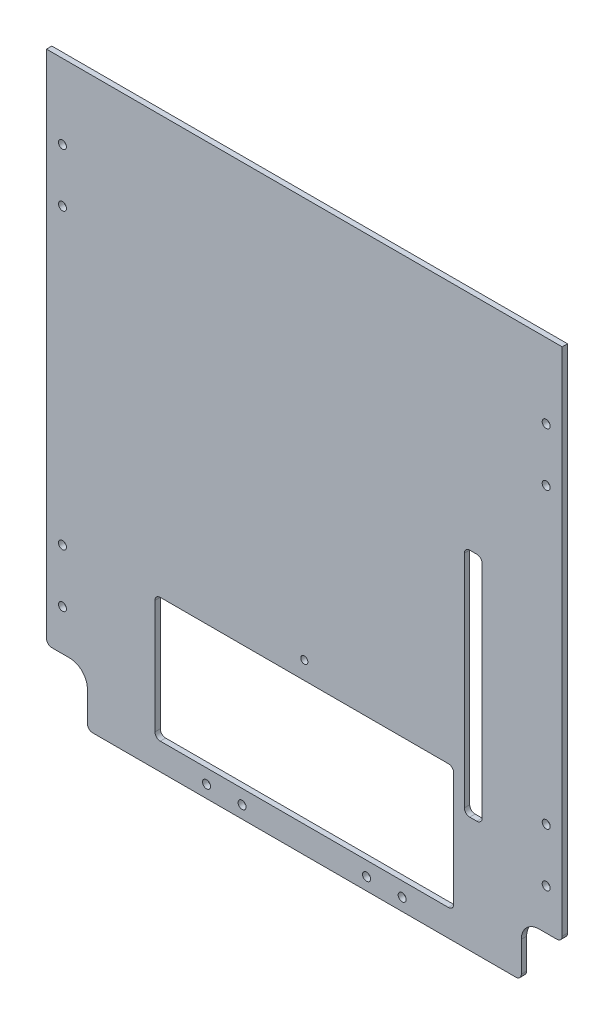
SolidWorks part; units mm, degrees
ref_plane "Front" through (0, 0, 0) normal (0, 0, 1) x (1, 0, 0)
ref_plane "Top" through (0, 0, 0) normal (0, 1, 0) x (1, 0, 0)
ref_plane "Right" through (0, 0, 0) normal (1, 0, 0) x (0, 0, -1)
sketch "Esquisse1" plane through (0, 0, 0) normal (0, 0, 1) x (1, 0, 0)
  line L1 (0, 0) -> (290, 0)
  line L2 (0, 0) -> (0, 320)
  line L3 (0, 320) -> (290, 320)
  line L4 (290, 0) -> (290, 320)
  dimension "D1" = 290
  dimension "D2" = 320
extrude "Boss.-Extru.1" add sketch "Esquisse1" along normal blind 3
sketch "Esquisse2" plane through (0, 0, 3) normal (0, 0, 1) x (1, 0, 0)
  line L0 (145, 0) -> (145, 172.6222) construction
  line L1 (290, 0) -> (267, 0)
  line L2 (290, 0) -> (290, 30)
  line L3 (290, 30) -> (267, 30)
  line L4 (267, 0) -> (267, 30)
  line L5 (0, 0) -> (290, 0) construction
  line L6 (23, 0) -> (23, 30)
  line L7 (0, 30) -> (23, 30)
  line L8 (0, 0) -> (0, 30)
  line L9 (0, 0) -> (23, 0)
  dimension "D1" = 23
  dimension "D2" = 30
extrude "Enlèv. mat.-Extru.1" cut sketch "Esquisse2" against normal through all both and the other way through all
fillet "Congé1" radius 10 2 edges at (23, 30, 1.5) (267, 30, 1.5)
fillet "Congé2" radius 3 4 edges at (267, 0, 1.5) (290, 30, 1.5) (23, 0, 1.5) (0, 30, 1.5)
sketch "Esquisse3" plane through (0, 0, 3) normal (0, 0, 1) x (1, 0, 0)
  line L0 (26, 0) -> (264, 0) construction
  line L1 (235, 195) -> (245, 195)
  line L2 (235, 195) -> (235, 65)
  line L3 (235, 65) -> (245, 65)
  line L4 (245, 195) -> (245, 65)
  dimension "D1" = 10
  dimension "D2" = 235
  dimension "D3" = 65
  dimension "D4" = 130
extrude "Enlèv. mat.-Extru.2" cut sketch "Esquisse3" against normal through all both and the other way through all
sketch "Esquisse4" plane through (0, 0, 3) normal (0, 0, 1) x (1, 0, 0)
  line L0 (26, 0) -> (264, 0) construction
  line L1 (61, 15) -> (229, 15)
  line L2 (61, 15) -> (61, 85)
  line L3 (61, 85) -> (229, 85)
  line L4 (229, 15) -> (229, 85)
  line L5 (145, 15) -> (145, 0) construction
  dimension "D1" = 70
  dimension "D2" = 15
  dimension "D3" = 168
extrude "Enlèv. mat.-Extru.3" cut sketch "Esquisse4" against normal through all both and the other way through all
fillet "Congé3" radius 3 8 edges at (235, 195, 1.5) (245, 195, 1.5) (245, 65, 1.5) (235, 65, 1.5) (229, 15, 1.5) (229, 85, 1.5) (61, 85, 1.5) (61, 15, 1.5)
sketch "Esquisse5" plane through (0, 0, 3) normal (0, 0, 1) x (1, 0, 0)
  line L0 (145, 0) -> (145, 95) construction
  line L1 (26, 0) -> (264, 0) construction
  line L2 (145, 7) -> (90, 7) construction
  circle A0 centre (145, 95) radius 2
  circle A1 centre (90, 7) radius 2.25
  circle A2 centre (110, 7) radius 2.25
  circle A3 centre (180, 7) radius 2.25
  circle A4 centre (200, 7) radius 2.25
  dimension "D1" = 4
  dimension "D3" = 110
  dimension "D4" = 4.5
  dimension "D6" = 20
  dimension "D2" = 95
  dimension "D5" = 7
extrude "Enlèv. mat.-Extru.4" cut sketch "Esquisse5" against normal through all both and the other way through all
sketch "Esquisse6" plane through (0, 0, 3) normal (0, 0, 1) x (1, 0, 0)
  line L0 (281, 308.1366) -> (281, -83.1051) construction
  line L2 (145, 0) -> (145, 67.282) construction
  line L3 (26, 0) -> (264, 0) construction
  line L4 (281, 165.5) -> (145, 165.5) construction
  line L5 (145, 320) -> (145, 263.6078) construction
  line L6 (290, 320) -> (0, 320) construction
  circle A0 centre (281, 83) radius 2.25
  circle A1 centre (281, 53) radius 2.25
  circle A2 centre (281, 278) radius 2.25
  circle A3 centre (281, 248) radius 2.25
  circle A4 centre (9, 248) radius 2.25
  circle A5 centre (9, 278) radius 2.25
  circle A6 centre (9, 53) radius 2.25
  circle A7 centre (9, 83) radius 2.25
  dimension "D2" = 4.5
  dimension "D3" = 30
  dimension "D4" = 53
  dimension "D5" = 195
  dimension "D1" = 136
extrude "Enlèv. mat.-Extru.5" cut sketch "Esquisse6" against normal through all both and the other way through all
